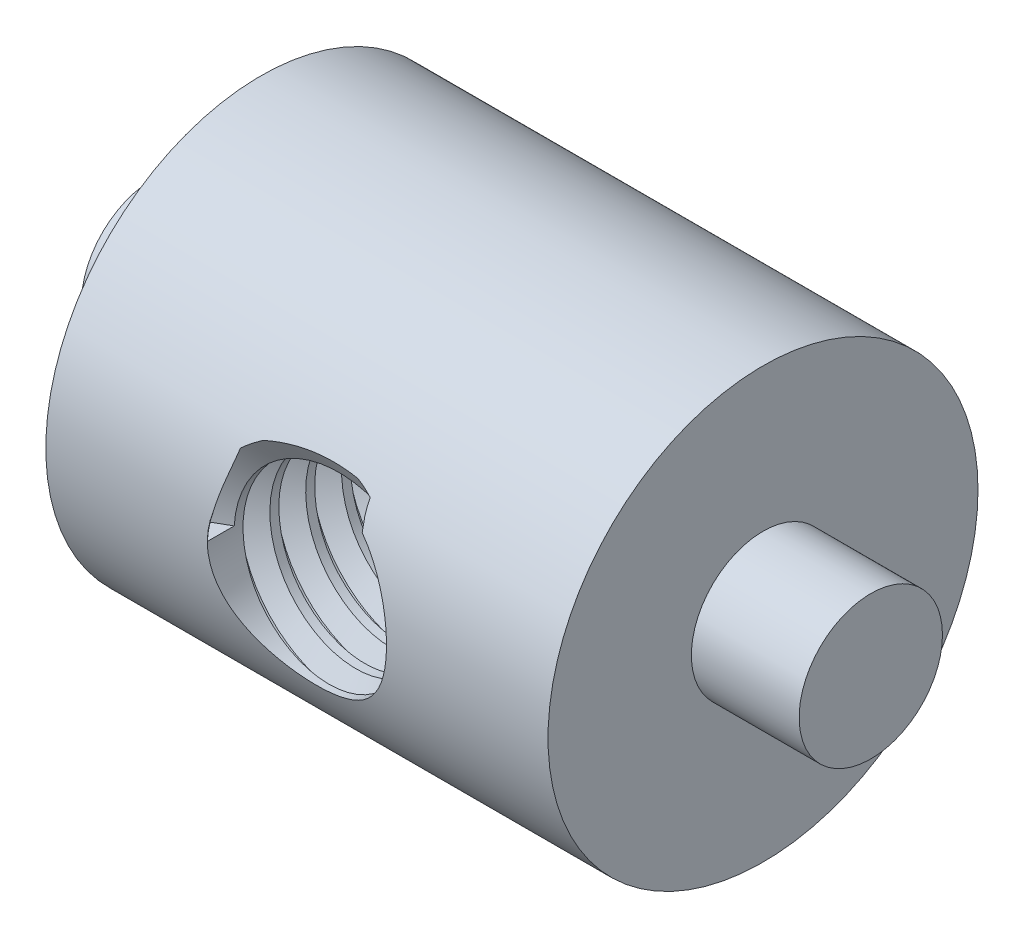
SolidWorks part; units mm, degrees
ref_plane "Front Plane" through (0, 0, 0) normal (0, 0, 1) x (1, 0, 0)
ref_plane "Top Plane" through (0, 0, 0) normal (0, 1, 0) x (1, 0, 0)
ref_plane "Right Plane" through (0, 0, 0) normal (1, 0, 0) x (0, 0, -1)
sketch "Sketch1" plane through (0, 0, 0) normal (1, 0, 0) x (0, 0, -1)
  circle A0 centre (0, 0) radius 9.525
  dimension "D1" = 19.05
extrude "Boss-Extrude1" add sketch "Sketch1" along normal mid plane 22.2504
sketch "Sketch2" plane through (11.1252, 0, 0) normal (1, 0, 0) x (0, 0, -1)
  circle A0 centre (0, 0) radius 3.175
  dimension "D1" = 6.35
extrude "Boss-Extrude2" add sketch "Sketch2" along normal blind 4.7752
mirror "Mirror1" about plane through (0, 0, 0) normal (1, 0, 0) of "Boss-Extrude2"
sketch "Sketch5" plane through (0, 0, 0) normal (0, 0, 1) x (1, 0, 0)
  circle A0 centre (0, 0) radius 3.9688
  dimension "D1" = 7.9375
extrude "Cut-Extrude1" cut sketch "Sketch5" against normal through all both and the other way through all
ref_plane "Plane3" through (0, 0, 9.525) normal (0, 0, 1) x (1, 0, 0)
thread "Thread2" pitch 1.5875 method cut profile "Thread Profile4" start angle 0, offset 0, length 19.05, pitch 1.5875, diameter 7.9375
ref_plane "Plane5" through (-3.9688, 0, 9.525) normal (0, -1, 0) x (-1, 0, 0)
sketch "Thread Profile4" plane through (-3.9688, 0, 9.525) normal (0, -1, 0) x (-1, 0, 0)
  line L0 (0, 0) -> (0, 1.5875) construction
  line L1 (0, 0) -> (0.8593, 0.4961)
  line L2 (0.8593, 0.4961) -> (0.8593, 0.6945)
  line L3 (0.8593, 0.6945) -> (0, 1.1906)
  line L4 (0.8593, 0.5953) -> (0, 0.5953) construction
  line L11 (0, 0) -> (0, 1.1906)
  point P2 (0, 0)
  dimension "Pitch" = 1.5875
  dimension "Profile_Angle" = 60
  dimension "Profile_Land" = 0.1984
  dimension "Profile_Height" = 0.8593
